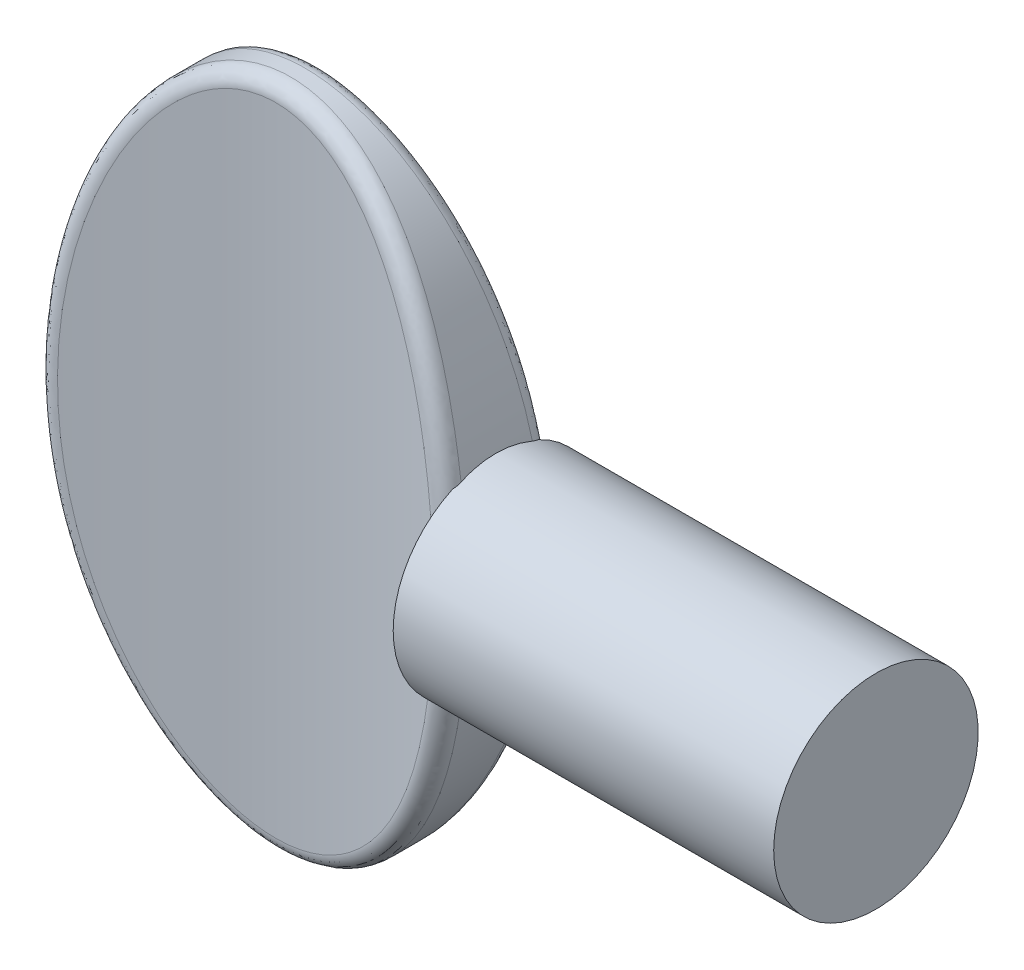
SolidWorks part; units mm, degrees
ref_plane "Front" through (0, 0, 0) normal (0, 0, 1) x (1, 0, 0)
ref_plane "Top" through (0, 0, 0) normal (0, 1, 0) x (1, 0, 0)
ref_plane "Right" through (0, 0, 0) normal (1, 0, 0) x (0, 0, -1)
ref_axis "Axis1" through (-50, 0, 0) along (1, 0, 0)
sketch "Sketch1" plane through (0, 0, 0) normal (0, 0, 1) x (1, 0, 0)
  line L0 (0, 0) -> (9.906, 0) construction
  line L1 (4.7413, -1.7526) -> (4.7413, 1.7526)
  line L2 (4.7413, -1.7526) -> (3.3847, -1.7526) construction
  ellipse E0 centre (0, 0) end of major axis (0, -5.715) minor radius 3.556
  dimension "D2" = 1.1853
  dimension "B" = 7.112
  dimension "L" = 6.35
extrude "Extrude1" add sketch "Sketch1" along normal mid plane 2.032
sketch "Sketch2" plane through (0, 0, 0) normal (0, 1, 0) x (1, 0, 0)
  line L0 (3.556, 1.016) -> (-3.556, 1.016) construction
  line L1 (0, 0) -> (0, 1.1721) construction
  line L2 (-1.7991, 0) -> (2.0444, 0) construction
  line L3 (-3.556, -1.016) -> (3.556, -1.016) construction
  line L6 (-3.556, 1.016) -> (-3.556, -1.016)
  line L7 (3.556, 1.016) -> (3.556, -1.016)
  arc A0 (-3.556, 1.016) -> (3.556, 1.016) centre (0, 10.6553) ccw
  arc A1 (-3.556, -1.016) -> (3.556, -1.016) centre (0, -10.6553) cw
extrude "Cut-Extrude1" cut sketch "Sketch2" against normal through all and the other way through all flip side to cut
fillet "Fillet3" radius 0.254 2 edges at (-3.4679, -1.2641, 0.984) (0.2073, 5.7053, -0.3831)
sketch "Sketch3" plane through (0, 0, 0) normal (0, 1, 0) x (1, 0, 0)
  line L1 (0, 0) -> (21.0288, 0) construction
  line L2 (0, 0) -> (9.906, 0) construction
  line L3 (4.7413, 1.7526) -> (4.7413, 0) construction
  line L4 (4.7413, 1.7526) -> (9.906, 1.7526)
  line L5 (9.906, 1.7526) -> (9.906, 0)
  line L6 (4.7413, 1.7526) -> (3.3847, 1.7526)
  line L7 (2.5775, 0.7096) -> (2.5775, 0)
  line L8 (3.3847, 0) -> (3.3847, 1.7526) construction
  line L9 (2.5775, 0) -> (9.906, 0)
  arc A0 (3.3847, 1.7526) -> (2.5775, 0.7096) centre (2.3072, 1.7526) cw
  arc A3 (-3.556, 1.016) -> (3.556, 1.016) centre (0, 10.6553) ccw construction
revolve "Revolve1" add sketch "Sketch3" angle 360 about L0
cosmetic thread "Cosmetic Thread1" [suppressed]
sketch "Sketch4" plane through (0, 0, 0) normal (0, 0, 1) x (1, 0, 0)
  line L0 (0, 0) -> (27.7993, 0) construction
  line L1 (9.7007, 1.7526) -> (9.906, 1.397)
  line L2 (9.906, 1.397) -> (10.1113, 1.7526)
  line L3 (10.1113, 1.7526) -> (10.1113, 2.1632)
  line L4 (10.1113, 2.1632) -> (9.7007, 2.1632)
  line L5 (9.7007, 2.1632) -> (9.7007, 1.7526)
  dimension "D1" = 2.794
  dimension "D2" = 3.5052
revolve "Cut-Revolve10" [suppressed] cut sketch "Sketch4" angle 360 about L0
pattern_linear "LPattern10" [suppressed] count 13 along (-1, 0, 0) of bodies 109
equation "\"D2@Sketch1\" = \"B@Sketch1\" / 6"
equation "\"D1@Fillet3\" = \"C1@Sketch2\" / 3"
equation "\"DIA@Sketch3\" = \"D@Sketch1\""
equation "\"D1@Cosmetic Thread1\" = \"L@Sketch1\""
equation "\"D1@Sketch4\" = \"D2@Cosmetic Thread1\""
equation "\"D2@Sketch4\" = \"DIA@Sketch3\""
equation "\"D1@LPattern10\" = \"D1@Cosmetic Thread1\" / \"P@LPattern10\" "
